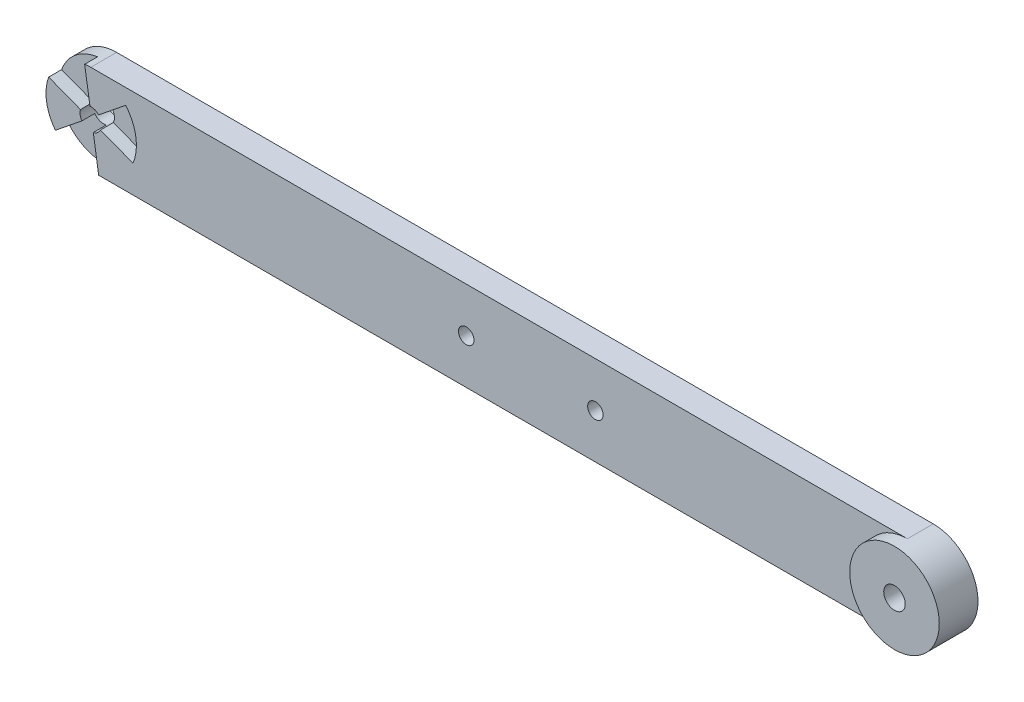
SolidWorks part; units mm, degrees
ref_plane "Front Plane" through (0, 0, 0) normal (0, 0, 1) x (1, 0, 0)
ref_plane "Top Plane" through (0, 0, 0) normal (0, 1, 0) x (1, 0, 0)
ref_plane "Right Plane" through (0, 0, 0) normal (1, 0, 0) x (0, 0, -1)
sketch "Sketch1" plane through (0, 0, 0) normal (0, 0, 1) x (1, 0, 0)
  line L0 (189.7, -10.4) -> (0, -10.4)
  line L1 (189.7, 10.4) -> (0, 10.4)
  circle A4 centre (0, 0) radius 2.5
  circle A5 centre (189.7, 0) radius 2.5
  arc A6 (0, 10.4) -> (0, -10.4) centre (0, 0) ccw
  arc A7 (189.7, -10.4) -> (189.7, 10.4) centre (189.7, 0) ccw
  arc A9 (0, -10.4) -> (0, 10.4) centre (0, 0) ccw construction
  circle A10 centre (0, 0) radius 10.4 construction
  arc A11 (189.7, 10.4) -> (189.7, -10.4) centre (189.7, 0) ccw construction
  circle A12 centre (189.7, 0) radius 10.4 construction
  circle A13 centre (189.7, 0) radius 1.4996 construction
  circle A15 centre (0, 0) radius 2.4001
  point P11 (170.2346, 97.4995)
  point P18 (75.4, 97.5)
  dimension "D1" = 5
  dimension "D3" = 1.0004
  dimension "D4" = 4.8001
  dimension "D2" = 10.4
  dimension "D5" = 189.7
extrude "Boss-Extrude1" add sketch "Sketch1" along normal blind 6 contours L0 A7 L1 A6 A4 A5 region at (94.85, 0, 0)
sketch "Sketch6" plane through (0, 0, 0) normal (0, 0, -1) x (-1, 0, 0)
  line L0 (0, 0) -> (6.6622, 8.2447) construction
  line L1 (0, 0) -> (-10.4, 0) construction
  line L2 (0, 0) -> (9.892, 3.8091) construction
  line L3 (0, 0) -> (1.6472, 10.4712) construction
  line L4 (2.3974, 0.7088) -> (9.9638, 3.6224)
  line L5 (0.1897, 2.4928) -> (1.4497, 10.5023)
  line L6 (-0.5848, -2.4306) -> (-1.8448, -10.4401)
  line L7 (0.0719, -0.1866) -> (9.9638, 3.6224) construction
  line L8 (-0.1976, 0.0311) -> (1.4497, 10.5023) construction
  line L9 (2.064, -1.4107) -> (8.3704, -6.5066)
  line L10 (0.1257, 0.1556) -> (8.3704, -6.5066) [skipped]
  line L11 (-0.1976, 0.0311) -> (-1.8448, -10.4401) [skipped]
  line L12 (0.0719, -0.1866) -> (-9.8201, -3.9957) [skipped]
  line L13 (0.1257, 0.1556) -> (-8.119, 6.8177) [skipped]
  line L14 (-1.8126, 1.7218) -> (-8.119, 6.8177)
  line L15 (-2.2537, -1.0821) -> (-9.8201, -3.9957)
  circle A0 centre (0, 0) radius 10.4 construction
  arc A1 (0, -10.4) -> (0, 10.4) centre (0, 0) ccw construction
  arc A2 (9.9621, 3.6217) -> (1.4494, 10.5004) centre (0, 0) ccw
  arc A3 (9.9621, 3.6217) -> (1.4494, 10.5004) centre (0, 0) ccw
  arc A4 (9.9621, 3.6217) -> (1.4494, 10.5004) centre (0, 0) ccw
  circle A5 centre (0, 0) radius 2.5 construction
  arc A6 (2.3974, 0.7088) -> (0.1897, 2.4928) centre (0, 0) ccw
  arc A7 (-0.5848, -2.4306) -> (2.064, -1.4107) centre (0, 0) ccw
  circle A8 centre (0, 0) radius 10.6 construction
  arc A9 (-1.8445, -10.4383) -> (8.369, -6.5054) centre (0, 0) ccw
  arc A10 (-1.8126, 1.7218) -> (-2.2537, -1.0821) centre (0, 0) ccw
  arc A11 (-8.1176, 6.8165) -> (-9.8183, -3.995) centre (0, 0) ccw
  point P8 (-0.7033, -1.0005)
  point P13 (7.6704, -5.9409)
  point P14 (0.0719, -0.1866)
  point P15 (9.124, 3.299)
  point P22 (10.1368, 3.0991)
  point P27 (0, 0)
  point P34 (0, 0)
  point P51 (0, 0)
  dimension "D3" = 60
  dimension "D2" = 128.94
  dimension "D4" = 30
  dimension "D6" = 0.2
  dimension "D8" = 3
  dimension "D1" = 0.2
  dimension "D5" = 0.2
  dimension "D7" = 3
extrude "Cut-Extrude3" cut sketch "Sketch6" against normal blind 3 contours L5 L4 | L9 L6 | L14 A11 L15 region at (-4.3826, 5.4237, 0) region at (-2.5057, -6.5073, 0) region at (6.8883, 1.0836, 0)
sketch "Sketch4" plane through (0, 0, 0) normal (0, 0, -1) x (-1, 0, 0)
  arc A0 (-189.7, 10.4) -> (-189.7, -10.4) centre (-189.7, 0) ccw construction
  arc A1 (-189.7, 10.4) -> (-189.7, -10.4) centre (-189.7, 0) ccw
  arc A2 (-189.7, 10.4) -> (-189.7, -10.4) centre (-189.7, 0) cw
  circle A3 centre (-189.7, 0) radius 2.5 construction
  circle A4 centre (-189.7, 0) radius 2.5
extrude "Boss-Extrude2" add sketch "Sketch4" along normal blind 3
mirror "Mirror1" about plane through (0, 0, 0) normal (0, 0, 1) of bodies 103
sketch "Sketch7" plane through (0, 0, -6) normal (0, 0, -1) x (-1, 0, 0)
  line L0 (-189.7, 10.4) -> (0, 10.4) construction
  line L1 (-189.7, -10.4) -> (0, -10.4) construction
  point P0 (-117.2212, -0.0523)
  point P3 (-87.2213, 0)
delete or keep bodies "Body-Delete/Keep 1" type delete bodies bodies 103
hole_wizard "M3 Clearance Hole1" positions "Sketch7" profile "Sketch8" hole size "M3" standard "ANSI Metric" end condition through all
sketch "Sketch8" plane through (117.2212, -0.0523, -6) normal (1, 0, 0) x (0, 1, 0)
  line L0 (0, 0) -> (0, 9)
  line L1 (0, 9) -> (1.8, 9)
  line L2 (1.8, 9) -> (1.8, 0)
  line L5 (1.8, 0) -> (0, 0)
  line L11 (0, -6.35) -> (0, 107.95) construction
  dimension "Thru Hole Dia." = 3.6
  dimension "Thru Hole Depth" = 9
